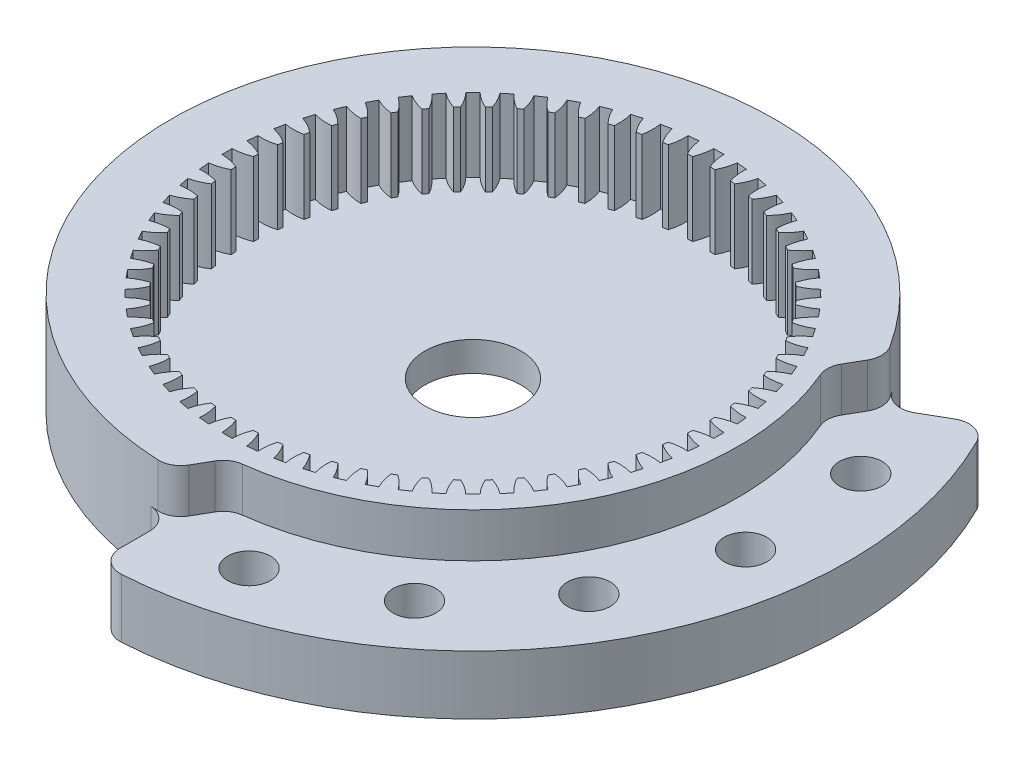
SolidWorks part; units mm, degrees
ref_plane "Front Plane" through (0, 0, 0) normal (0, 0, 1) x (1, 0, 0)
ref_plane "Top Plane" through (0, 0, 0) normal (0, 1, 0) x (1, 0, 0)
ref_plane "Right Plane" through (0, 0, 0) normal (1, 0, 0) x (0, 0, -1)
sketch "Sketch1" plane through (0, 0, 0) normal (0, 1, 0) x (1, 0, 0)
  circle A0 centre (0, 0) radius 16
  circle A1 centre (0, 0) radius 16.7
  circle A2 centre (0, 0) radius 15.5
  dimension "D1" = 32
  dimension "D2" = 33.4
  dimension "D3" = 1.2
extrude "Boss-Extrude1" add sketch "Sketch1" along normal mid plane 5 contours A1 A0 | A0 A2 | A2 region at (-15.5475, 0, 0) region at (-16.2277, 0, 0) region at (0, 0, 0)
sketch "Sketch7" plane through (0, 0, 0) normal (0, 1, 0) x (1, 0, 0)
  line L0 (16.7, 0) -> (-16.7, 0) construction
  line L1 (0, 16.7) -> (0, -16.7) construction
  circle A0 centre (0, 0) radius 16.7 construction
  point P7 (0, 0)
sketch "Sketch4" plane through (0, 0, 0) normal (0, 1, 0) x (1, 0, 0)
  line L0 (0, 0) -> (0, -25.5) construction
  line L10 (0, 0) -> (22.0836, 12.75) construction
  line L11 (22.0836, 12.75) -> (17.7535, 10.25)
  line L12 (0, -25.5) -> (0, -20.5)
  circle A2 centre (0, 0) radius 15.5 construction
  circle A3 centre (0, 0) radius 15.5
  arc A4 (17.7535, 10.25) -> (0, -20.5) centre (0, 0) ccw
  circle A9 centre (0, 0) radius 25.5 construction
  arc A10 (22.0836, 12.75) -> (0, -25.5) centre (0, 0) cw
  dimension "D1" = 5
  dimension "D3" = 120
  dimension "D2" = 5
extrude "Boss-Extrude2" add sketch "Sketch4" along normal mid plane 5
sketch "Sketch3" plane through (0, 0, 0) normal (0, 1, 0) x (1, 0, 0)
  line L0 (0, 0) -> (0, 16.7) construction
  line L1 (-0.3927, 15.9952) -> (0.3927, 15.9952) construction
  line L2 (-0.3434, 15.4962) -> (0, 0) construction
  line L3 (0, 13.7683) -> (-0.5155, 16.692) construction
  line L4 (0, 0) -> (0.8194, 16.6799) construction
  line L5 (0.3927, 15.9952) -> (1.177, 15.9566) construction
  line L6 (0, 15.5) -> (0, 16.7) construction
  line L7 (0.3434, 15.4962) -> (0.3434, 16.7) construction
  line L8 (0.3434, 16.0981) -> (-0.3121, 16.0981) construction
  arc A1 (-0.5957, 16.6894) -> (-0.3434, 15.4962) centre (-3.6364, 15.4232) cw construction
  arc A2 (0.5957, 16.6894) -> (0.3434, 15.4962) centre (3.6364, 15.4232) ccw construction
  circle A3 centre (0, 0) radius 15.5 construction
  arc A4 (0.3434, 15.4962) -> (-0.3434, 15.4962) centre (0, 0) ccw construction
  circle A5 centre (0, 0) radius 16 construction
  circle A6 centre (0, 0) radius 16.7 construction
  arc A7 (0.5957, 15.5068) -> (-0.5957, 15.5068) centre (0, 32.1962) cw
  arc A8 (0.5957, 16.6894) -> (-0.5957, 16.6894) centre (0, 0) ccw construction
  arc A9 (-0.5957, 15.5068) -> (-0.3434, 16.7) centre (-3.6364, 16.773) ccw
  arc A10 (0.5957, 15.5068) -> (0.3434, 16.7) centre (3.6364, 16.773) cw
  arc A11 (0.3434, 16.7) -> (-0.3434, 16.7) centre (0, 32.1962) cw
  dimension "D3" = 2.813
  dimension "D2" = 10
extrude "Cut-Extrude1" cut sketch "Sketch3" against normal through all both and the other way through all
pattern_circular "CirPattern1" count 64 over 360 about axis through (0, 2.5, 0) along (0, 1, 0) of "Cut-Extrude1"
sketch "Sketch5" plane through (0, 0, 0) normal (0, 1, 0) x (1, 0, 0)
  circle A0 centre (0, 0) radius 15.5183
extrude "Cut-Extrude2" cut sketch "Sketch5" against normal through all both and the other way through all
sketch "Sketch8" plane through (0, -2.5, 0) normal (0, -1, 0) x (1, 0, 0)
  line L2 (0, 25.5) -> (0, 20.5)
  line L6 (0, 25.5) -> (0, 20.5)
  line L8 (17.7535, -10.25) -> (22.0836, -12.75)
  line L9 (17.7535, -10.25) -> (22.0836, -12.75)
  circle A0 centre (0, 0) radius 3.25
  arc A3 (22.0836, -12.75) -> (0, 25.5) centre (0, 0) ccw
  arc A4 (22.0836, -12.75) -> (0, 25.5) centre (0, 0) ccw
  arc A5 (0, 20.5) -> (17.7535, -10.25) centre (0, 0) ccw
  arc A7 (0, 20.5) -> (17.7535, -10.25) centre (0, 0) ccw
  dimension "D2" = 6.5
  dimension "D1" = 0
extrude "Boss-Extrude3" add sketch "Sketch8" along normal blind 2
sketch "Sketch6" plane through (0, 2.5, 0) normal (0, 1, 0) x (1, 0, 0)
  line L0 (0, 0) -> (5.5646, -20.7674) construction
  line L2 (0, -16.7) -> (0, 16.7) construction
  circle A3 centre (5.5646, -20.7674) radius 0.5
  point P11 (0, 0)
  dimension "D2" = 15
  dimension "D1" = 1
  dimension "D3" = 21.5
extrude "Cut-Extrude3" cut sketch "Sketch6" against normal through all
pattern_circular "CirPattern2" count 5 every 22.5 about axis through (0, -2.5, 0) along (0, -1, 0) of "Cut-Extrude3" reverse direction yes
sketch "Sketch9" plane through (0, 2.5, 0) normal (0, 1, 0) x (1, 0, 0)
  line L0 (17.7535, 10.25) -> (16.275, 7.6892)
  line L1 (0, -20.5) -> (1.4785, -17.9392)
  line L2 (0, 0) -> (18.6195, -10.75) construction
  line L3 (1.4785, -17.9392) -> (16.275, 7.6892) construction
  line L4 (17.7535, 10.25) -> (22.0836, 12.75)
  line L5 (0, -20.5) -> (0, -25.5)
  arc A0 (1.4785, -17.9392) -> (16.275, 7.6892) centre (0, 0) ccw
  arc A1 (0, -25.5) -> (22.0836, 12.75) centre (0, 0) ccw construction
  arc A2 (0, -25.5) -> (22.0836, 12.75) centre (0, 0) ccw
  point P5 (8.8768, -5.125)
  dimension "D1" = 36
extrude "Cut-Extrude4" cut sketch "Sketch9" against normal offset from surface (3 mm away) 4 up to face at (13.2797, -4.5, 17.519)
fillet "Fillet1" radius 1.5 6 edges at (17.7535, -2.5, -10.25) (22.0836, -2.5, -12.75) (0, -2.5, 25.5) (0, -2.5, 20.5) (16.275, 1, -7.6892) (1.4785, 1, 17.9392)
fillet "Fillet2" radius 1.5 2 edges at (0, 1, 20.5) (17.7535, 1, -10.25)
sketch "Sketch12" plane through (0, -4.5, 0) normal (0, -1, 0) x (-1, 0, 0)
  point P0 (-5.5646, -20.7674)
  point P3 (-13.0884, -17.0571)
  point P6 (-18.6195, -10.75)
  point P9 (-21.3161, -2.8063)
  point P12 (-20.7674, 5.5646)
hole_wizard "CSK for M2.5 Countersunk Flat Head Screw1" positions "Sketch12" profile "Sketch11" countersink size "M2.5" standard "ISO"
sketch "Sketch11" plane through (5.5646, -4.5, 20.7674) normal (1, 0, 0) x (0, 0, -1)
  line L0 (0, 0) -> (0, 4.8712)
  line L1 (0, 4.8712) -> (1.45, 4)
  line L2 (1.45, 4) -> (1.45, 1.3)
  line L3 (1.45, 1.3) -> (2.75, 0)
  line L5 (2.75, 0) -> (0, 0)
  line L6 (-1.45, 1.3) -> (-2.75, 0) construction
  line L10 (0, 4.8712) -> (-1.45, 4) construction
  line L11 (0, -6.35) -> (0, 107.95) construction
  dimension "Hole Dia." = 2.9
  dimension "Hole Depth" = 4
  dimension "Near C'Sink Dia." = 5.5
  dimension "Near C'Sink Angle" = 90
  dimension "Drill Angle" = 118
ref_axis "Axis1" through (18.6195, -0.5, 10.75) along (0, -1, 0)
ref_axis "Axis2" through (0, -4.5, 0) along (0, 1, 0)
ref_plane "Plane1" through (0, 0, 0) normal (0.5, 0, -0.866) x (-0.866, 0, -0.5)
equation "\"Module\"= .5"
equation "\"Number of Teeth\"=64"
equation "\"D1@Sketch1\"=\"Module\"* \"Number of Teeth\""
equation "\"D2@Sketch1\"=(\"Number of Teeth\" + 2) * \"Module\" + .4"
equation "\"D3@Sketch1\"=\"Module\" * if( \"Module\" => 1.25, 2.25, 2.4)"
equation "\"D3@Sketch3\"=180 / \"Number of Teeth\""
equation "\"D1@CirPattern1\"=\"Number of Teeth\""
